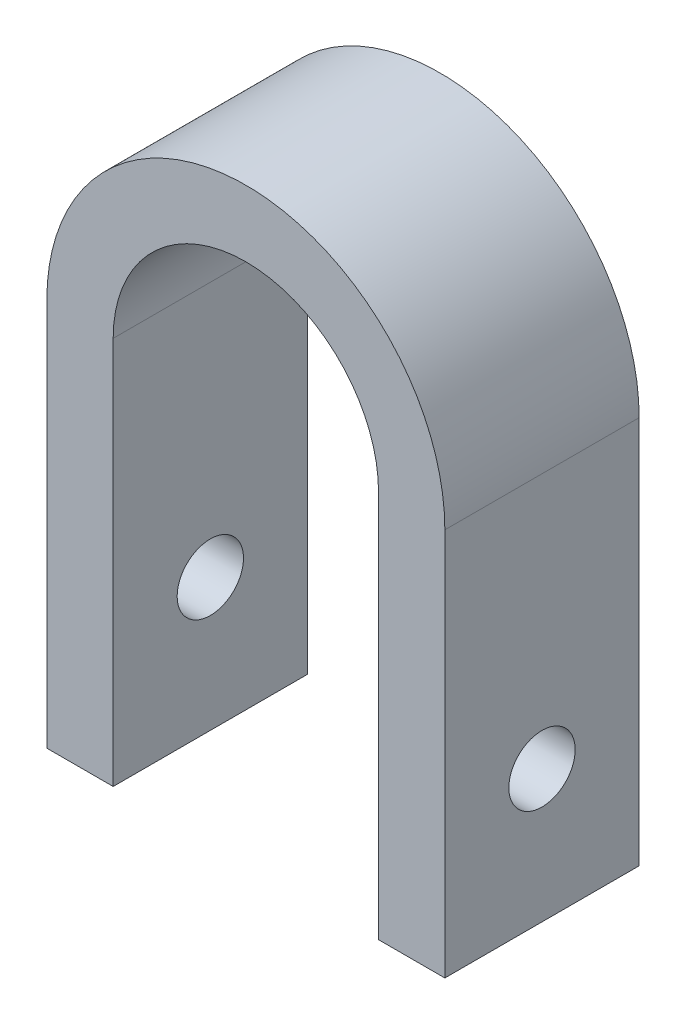
SolidWorks part; units mm, degrees
ref_plane "Front Plane" through (0, 0, 0) normal (0, 0, 1) x (1, 0, 0)
ref_plane "Top Plane" through (0, 0, 0) normal (0, 1, 0) x (1, 0, 0)
ref_plane "Right Plane" through (0, 0, 0) normal (1, 0, 0) x (0, 0, -1)
sketch "Sketch1" plane through (0, 0, 0) normal (0, 0, 1) x (1, 0, 0)
  line L0 (-4, 0) -> (-4, -11.7015)
  line L1 (-4, -1.0579) -> (-4, -25) construction
  line L3 (4, -21.6) -> (4, -1.0579) construction
  line L4 (-6, 0) -> (-6, -11.7015)
  line L5 (-6, -11.7015) -> (-4, -11.7015)
  line L6 (4, 0) -> (4, -11.7015)
  line L7 (6, 0) -> (6, -11.7015)
  line L8 (6, -11.7015) -> (4, -11.7015)
  arc A0 (4, 0) -> (-4, 0) centre (0, 0) ccw
  arc A1 (6, 0) -> (-6, 0) centre (0, 0) ccw
  dimension "D2" = 12
extrude "Boss-Extrude1" add sketch "Sketch1" along normal blind 5.8581
sketch "Sketch2" plane through (-6, 0, 0) normal (-1, 0, 0) x (0, 0, 1)
  line L0 (0, -11.7015) -> (2.9291, -7.7015) construction
  line L1 (2.9291, -7.7015) -> (5.8581, -11.7015) construction
  line L2 (5.8581, -11.7015) -> (0, -11.7015) construction
  circle A0 centre (2.9291, -7.7015) radius 1
  dimension "D2" = 2
  dimension "D1" = 4
extrude "Cut-Extrude1" cut sketch "Sketch2" against normal through all
